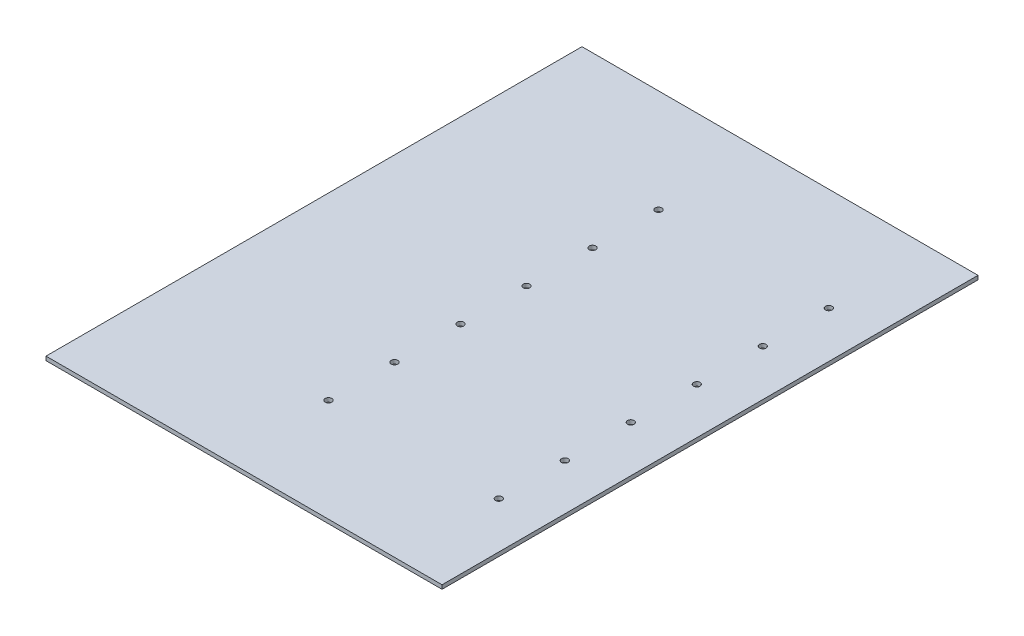
SolidWorks part; units mm, degrees
ref_plane "Front Plane" through (0, 0, 0) normal (0, 0, 1) x (1, 0, 0)
ref_plane "Top Plane" through (0, 0, 0) normal (0, 1, 0) x (1, 0, 0)
ref_plane "Right Plane" through (0, 0, 0) normal (1, 0, 0) x (0, 0, -1)
sketch "Sketch1" plane through (0, 0, 0) normal (0, 1, 0) x (1, 0, 0)
  line L1 (-150, -203) -> (150, -203)
  line L2 (-150, -203) -> (-150, 203)
  line L3 (-150, 203) -> (150, 203)
  line L4 (150, -203) -> (150, 203)
  line L5 (-150, -203) -> (150, 203) construction
  line L6 (-150, 203) -> (150, -203) construction
  point P0 (0, 0)
  dimension "D1" = 406
  dimension "D2" = 300
extrude "Boss-Extrude1" add sketch "Sketch1" along normal blind 3
sketch "Sketch2" plane through (0, 3, 0) normal (0, 1, 0) x (1, 0, 0)
  line L0 (0, -1000) -> (0, 49000) construction
  line L1 (115, -1000) -> (115, 49000) construction
  line L2 (150, -203) -> (150, 203) construction
  line L3 (150, 203) -> (-150, 203) construction
  line L6 (115, 125) -> (-14, 125) construction
  circle A0 centre (115, 125) radius 2.5
  circle A1 centre (115, 75) radius 2.5
  circle A2 centre (115, 25) radius 2.5
  circle A3 centre (115, -25) radius 2.5
  circle A4 centre (115, -75) radius 2.5
  circle A5 centre (115, -125) radius 2.5
  circle A12 centre (-14, 125) radius 2.5
  circle A13 centre (-14, 75) radius 2.5
  circle A14 centre (-14, 25) radius 2.5
  circle A15 centre (-14, -25) radius 2.5
  circle A16 centre (-14, -75) radius 2.5
  circle A17 centre (-14, -125) radius 2.5
  dimension "D2" = 78
  dimension "D3" = 5
  dimension "D5" = 50
  dimension "D6" = 2
  dimension "D1" = 35
  dimension "D7" = 129
  dimension "D4" = 6
extrude "Cut-Extrude1" cut sketch "Sketch2" against normal up to next
